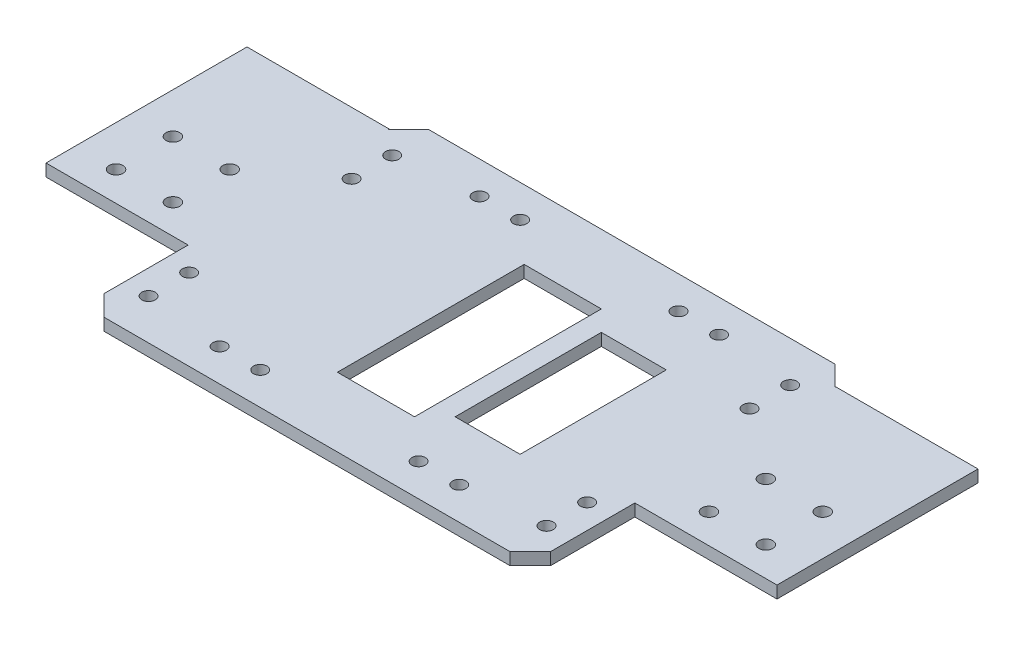
SolidWorks part; units mm, degrees
material "PLA+ esun"
ref_plane "Front Plane" through (0, 0, 0) normal (0, 0, 1) x (1, 0, 0)
ref_plane "Top Plane" through (0, 0, 0) normal (0, 1, 0) x (1, 0, 0)
ref_plane "Right Plane" through (0, 0, 0) normal (1, 0, 0) x (0, 0, -1)
sketch "Sketch1" plane through (0, 0, 0) normal (0, 1, 0) x (1, 0, 0)
  line L0 (0, 0) -> (0, -22.4966) construction
  line L1 (-100, 40) -> (100, 40)
  line L2 (-100, 40) -> (-100, -40)
  line L3 (-100, -40) -> (100, -40)
  line L4 (100, 40) -> (100, -40)
  line L5 (-100, 40) -> (100, -40) construction
  line L6 (-100, -40) -> (100, 40) construction
  line L7 (-9.5, 23) -> (9.5, 23)
  line L8 (-9.5, 23) -> (-9.5, -23)
  line L9 (-9.5, -23) -> (9.5, -23)
  line L10 (9.5, 23) -> (9.5, -23)
  line L11 (-9.5, 23) -> (9.5, -23) construction
  line L12 (-9.5, -23) -> (9.5, 23) construction
  line L13 (-90, 14.25) -> (-56, 14.25)
  line L14 (-90, 14.25) -> (-90, -14.25)
  line L15 (-90, -14.25) -> (-56, -14.25)
  line L16 (-56, 14.25) -> (-56, -14.25)
  line L17 (-90, 14.25) -> (-56, -14.25) construction
  line L18 (-90, -14.25) -> (-56, 14.25) construction
  line L19 (-80, 7) -> (-66, 7)
  line L20 (-80, 7) -> (-80, -7)
  line L21 (-80, -7) -> (-66, -7)
  line L22 (-66, 7) -> (-66, -7)
  line L23 (-80, 7) -> (-66, -7) construction
  line L24 (-80, -7) -> (-66, 7) construction
  line L25 (80, -7) -> (66, 7) construction
  line L26 (80, 7) -> (66, -7) construction
  line L27 (90, -14.25) -> (56, 14.25) construction
  line L28 (90, 14.25) -> (56, -14.25) construction
  line L29 (100, -40) -> (-100, 40) construction
  line L30 (100, 40) -> (-100, -40) construction
  line L31 (66, 7) -> (66, -7)
  line L32 (80, -7) -> (66, -7)
  line L33 (80, 7) -> (80, -7)
  line L34 (80, 7) -> (66, 7)
  line L35 (56, 14.25) -> (56, -14.25)
  line L36 (90, -14.25) -> (56, -14.25)
  line L37 (90, 14.25) -> (90, -14.25)
  line L38 (90, 14.25) -> (56, 14.25)
  line L39 (-100, -30.3979) -> (-77.5, -30.3979) construction
  line L40 (-77.5, -30.3979) -> (-55, -30.3979) construction
  line L41 (0, 0) -> (18.7357, 0) construction
  line L42 (-100, -40) -> (-55, -40)
  line L43 (-100, -40) -> (-100, -14.25)
  line L44 (-100, -14.25) -> (-55, -14.25)
  line L45 (-55, -40) -> (-55, -14.25)
  line L46 (55, -40) -> (55, -14.25)
  line L47 (100, -14.25) -> (55, -14.25)
  line L48 (-100, 14.25) -> (-55, 14.25)
  line L49 (100, 14.25) -> (55, 14.25)
  line L50 (55, 40) -> (55, 14.25)
  line L51 (-55, 40) -> (-55, 14.25)
  line L57 (14.5, 18) -> (30.5, 18)
  line L58 (14.5, 18) -> (14.5, -18)
  line L59 (14.5, -18) -> (30.5, -18)
  line L60 (30.5, 18) -> (30.5, -18)
  circle A1 centre (-80, 7) radius 1.7
  circle A2 centre (-66, 7) radius 1.7
  circle A3 centre (-66, -7) radius 1.7
  circle A4 centre (-80, -7) radius 1.7
  circle A5 centre (-80, 7) radius 2.75
  circle A6 centre (80, 7) radius 2.75
  circle A7 centre (80, -7) radius 1.7
  circle A8 centre (66, -7) radius 1.7
  circle A9 centre (66, 7) radius 1.7
  circle A10 centre (80, 7) radius 1.7
  point P0 (0, 0)
  point P6 (0, 0)
  point P11 (-73, 0)
  point P18 (-73, 0)
  point P44 (73, 0)
  dimension "D9" = 2
  dimension "D10" = 2
  dimension "D13" = 45
  dimension "D2" = 80
  dimension "D3" = 19
  dimension "D4" = 46
  dimension "D5" = 34
  dimension "D6" = 28.5
  dimension "D7" = 25.75
  dimension "D8" = 10
  dimension "D11" = 14
  dimension "D12" = 14
  dimension "D14" = 22.5
  dimension "D15" = 200
  dimension "D16" = 25.75
  dimension "D17" = 5
  dimension "D18" = 5
  dimension "D19" = 5
  dimension "D20" = 16
extrude "Boss-Extrude1" add sketch "Sketch1" along normal blind 3 contours L4 L1 L2 L3 L38 L37 L36 L35 L7 L10 L9 L8 L13 L16 L15 L14 | L16 L13 L14 L15 A5 L19 A2 L22 A3 L21 A4 L20 | L37 L38 L35 L36 L31 A9 L34 A6 L33 A7 L32 A8 | L19 A5 L20 A1 | L34 A10 L33 A6 | A5 L20 A4 L21 A3 L22 A2 L19 | L20 A5 L19 A1 | L34 A9 L31 A8 L32 A7 L33 A6 | L33 A10 L34 A6 region at (0, 0, -38.6236) region at (-73, 0, -13.8064) region at (73, 0, -13.8064) region at (-81.2571, 0, -8.2571) region at (-78.5572, 0, -5.5572) region at (-72.8887, 0, 0.1113) region at (72.8887, 0, 0.1113) region at (80, 0, -9.6722) region at (78.5572, 0, -5.5572)
sketch "Sketch4" plane through (0, 3, 0) normal (0, 1, 0) x (1, 0, 0)
  line L2 (-9.5, 23) -> (9.5, 23) construction
  line L4 (9.5, 23) -> (9.5, -23) construction
  line L5 (0, 0) -> (38.0714, 0) construction
  line L6 (0, 0) -> (0, -7.3126) construction
  circle A0 centre (29.5, 32) radius 1.65
  circle A1 centre (19.5, 32) radius 1.65
  circle A2 centre (19.5, -32) radius 1.65
  circle A3 centre (29.5, -32) radius 1.65
  circle A4 centre (-19.5, 32) radius 1.65
  circle A5 centre (-29.5, 32) radius 1.65
  circle A6 centre (-29.5, -32) radius 1.65
  circle A7 centre (-19.5, -32) radius 1.65
  dimension "D1" = 3.3
  dimension "D2" = 9
  dimension "D3" = 20
  dimension "D5" = 10
  dimension "D4" = 2
extrude "Cut-Extrude2" cut sketch "Sketch4" against normal blind 15
sketch "Sketch5" plane through (0, 3, 0) normal (0, 1, 0) x (1, 0, 0)
  line L8 (-55, 40) -> (-55, 14.25) construction
  line L9 (-55, 40) -> (55, 40) construction
  circle A0 centre (-49, 30) radius 1.65
  circle A1 centre (-49, -20) radius 1.65
  circle A2 centre (-49, -30) radius 1.65
  circle A3 centre (-49, 20) radius 1.65
  circle A4 centre (49, 20) radius 1.65
  circle A5 centre (49, -30) radius 1.65
  circle A6 centre (49, -20) radius 1.65
  circle A7 centre (49, 30) radius 1.65
  point P0 (0, 0)
  dimension "D1" = 3.3
  dimension "D2" = 6
  dimension "D3" = 10
  dimension "D5" = 10
  dimension "D4" = 2
extrude "Cut-Extrude3" cut sketch "Sketch5" against normal blind 10
chamfer "Chamfer1" distance 5 angle 45 4 edges at (-55, 1.5, -40) (55, 1.5, -40) (55, 1.5, 40) (-55, 1.5, 40)
sketch "Sketch6" plane through (0, 3, 0) normal (0, 1, 0) x (1, 0, 0)
  line L0 (-55, 35) -> (-55, 14.25) construction
  line L1 (-90, 14.25) -> (-55, 14.25)
  line L2 (-90, 14.25) -> (-90, 35.25)
  line L3 (-90, 35.25) -> (-55, 35.25)
  line L4 (-55, 14.25) -> (-55, 35.25)
  line L5 (0, 0) -> (0, -16.9575) construction
  line L6 (55, 14.25) -> (55, 35.25)
  line L7 (90, 35.25) -> (55, 35.25)
  line L8 (90, 14.25) -> (90, 35.25)
  line L9 (90, 14.25) -> (55, 14.25)
  dimension "D1" = 21
extrude "Boss-Extrude2" add sketch "Sketch6" against normal blind 3
